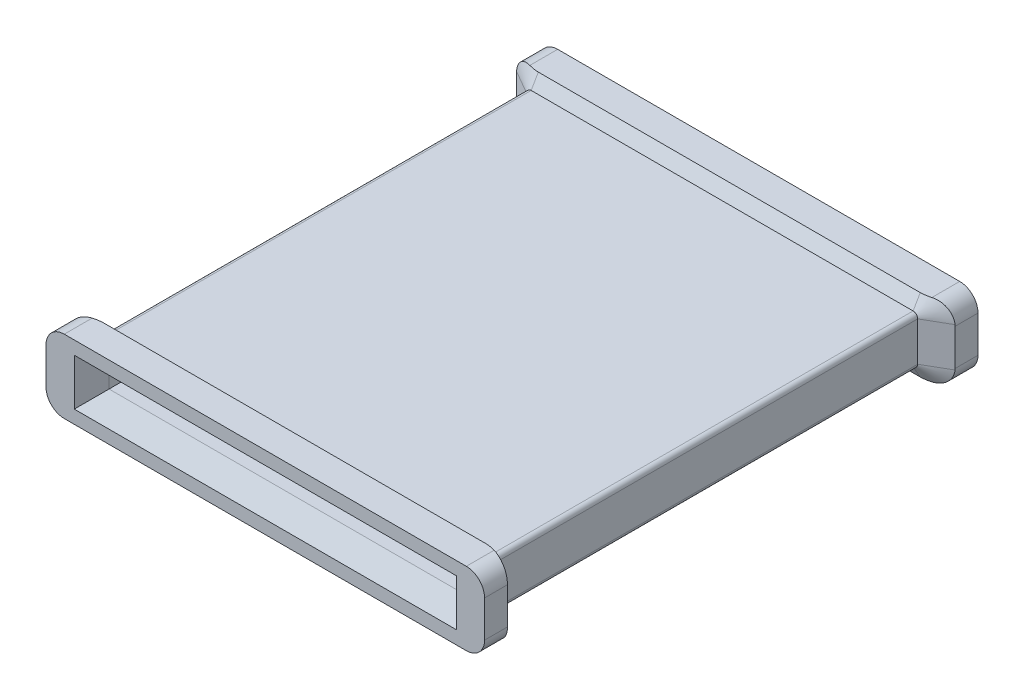
SolidWorks part; units mm, degrees
material "ABS"
ref_plane "Front Plane" through (0, 0, 0) normal (0, 0, 1) x (1, 0, 0)
ref_plane "Top Plane" through (0, 0, 0) normal (0, 1, 0) x (1, 0, 0)
ref_plane "Right Plane" through (0, 0, 0) normal (1, 0, 0) x (0, 0, -1)
sketch "Sketch1" plane through (0, 0, 0) normal (0, 0, 1) x (1, 0, 0)
  line L0 (0, 8) -> (48, 8)
  line L3 (48, 8) -> (48, 0)
  line L4 (48, 0) -> (0, 0)
  line L5 (0, 0) -> (0, 8)
  line L9 (3.4, 6.25) -> (44.6, 6.25)
  line L10 (3.4, 6.25) -> (3.4, 1.75)
  line L11 (3.4, 1.75) -> (44.6, 1.75)
  line L12 (44.6, 6.25) -> (44.6, 1.75)
  dimension "D1" = 1.75
  dimension "D2" = 41.2
  dimension "D4" = 4.5
  dimension "D5" = 1.75
  dimension "D7" = 3.4
  dimension "D8" = 3.4
extrude "Boss-Extrude1" add sketch "Sketch1" along normal blind 54
sketch "Sketch2" plane through (0, 0, 54) normal (0, 0, 1) x (1, 0, 0)
  line L1 (3.1, 6.65) -> (44.9, 6.65)
  line L2 (2.6, 6.15) -> (2.6, 1.85)
  line L3 (3.1, 1.35) -> (44.9, 1.35)
  line L4 (45.4, 6.15) -> (45.4, 1.85)
  line L5 (3.4, 1.75) -> (44.6, 1.75) construction
  line L6 (44.6, 6.25) -> (3.4, 6.25) construction
  line L8 (3.4, 6.25) -> (3.4, 1.75) construction
  line L9 (44.6, 1.75) -> (44.6, 6.25) construction
  arc A0 (2.6, 1.85) -> (3.1, 1.35) centre (3.1, 1.85) ccw
  arc A1 (44.9, 1.35) -> (45.4, 1.85) centre (44.9, 1.85) ccw
  arc A2 (44.9, 6.65) -> (45.4, 6.15) centre (44.9, 6.15) cw
  arc A3 (3.1, 6.65) -> (2.6, 6.15) centre (3.1, 6.15) ccw
  dimension "D1" = 0.5
  dimension "D2" = 0.4
  dimension "D3" = 0.8
  dimension "D4" = 0.8
  dimension "D5" = 0.4
extrude "Cut-Extrude1" cut sketch "Sketch2" against normal offset from surface (50 mm away) 2 from offset 2 flip side to cut up to face at (24, 4, 0) offset against normal yes
fillet "Fillet1" radius 2 8 edges at (48, 8, 53) (48, 0, 53) (48, 0, 1) (48, 8, 1) (0, 0, 1) (0, 8, 1) (0, 0, 53) (0, 8, 53)
chamfer "Chamfer4" distance 2 angle 60 16 edges at (2.6, 4, 52) (2.7464, 1.4964, 52) (2.7464, 6.5036, 52) (24, 1.35, 52) (24, 6.65, 52) (45.2536, 1.4964, 52) (45.2536, 6.5036, 52) (45.4, 4, 52) (2.6, 4, 2) (2.7464, 1.4964, 2) (2.7464, 6.5036, 2) (24, 1.35, 2) (24, 6.65, 2) (45.2536, 1.4964, 2) (45.2536, 6.5036, 2) (45.4, 4, 2) first distance on face at (2.6, 4, 27) first distance on face at (2.7982, 1.5482, 27) first distance on face at (2.7982, 6.4518, 27) first distance on face at (24, 1.35, 27) first distance on face at (24, 6.65, 27) first distance on face at (45.2018, 1.5482, 27) first distance on face at (45.2018, 6.4518, 27) first distance on face at (45.4, 4, 27)
chamfer "Chamfer5" distance 3.5 angle 5 8 edges at (44.6, 4, 54) (24, 1.75, 54) (3.4, 4, 54) (24, 6.25, 54) (44.6, 4, 0) (24, 1.75, 0) (3.4, 4, 0) (24, 6.25, 0) first distance on face at (44.6, 4, 27) first distance on face at (24, 1.75, 27) first distance on face at (3.4, 4, 27) first distance on face at (24, 6.25, 27)
